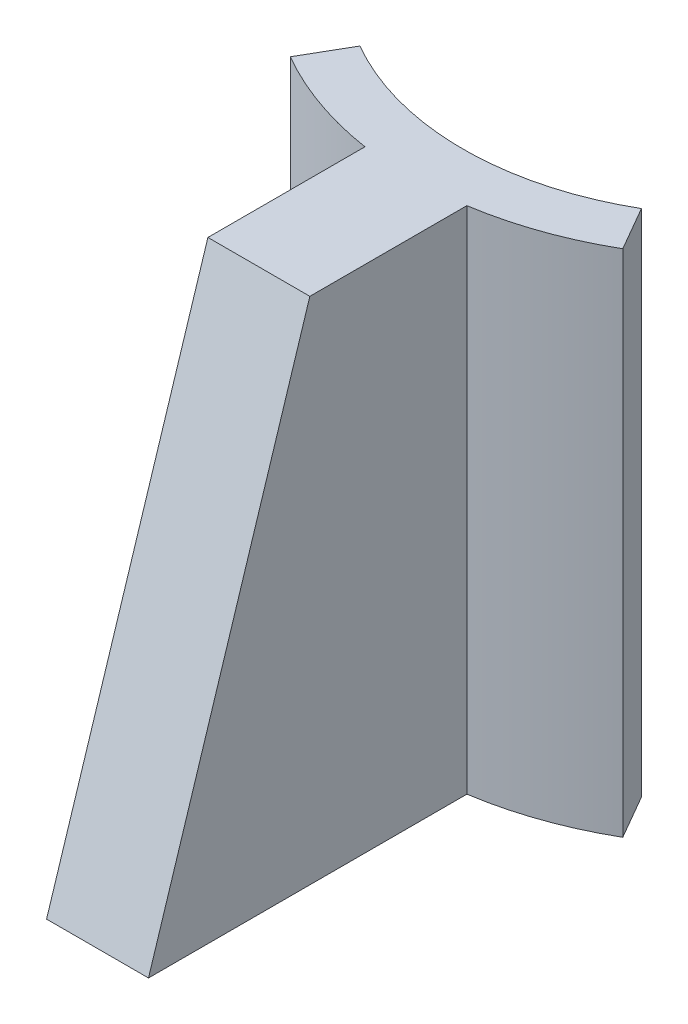
SolidWorks part; units mm, degrees
ref_plane "Front Plane" through (0, 0, 0) normal (0, 0, 1) x (1, 0, 0)
ref_plane "Top Plane" through (0, 0, 0) normal (0, 1, 0) x (1, 0, 0)
ref_plane "Right Plane" through (0, 0, 0) normal (1, 0, 0) x (0, 0, -1)
sketch "Sketch1" plane through (0, 0, 0) normal (1, 0, 0) x (0, 0, -1)
  line L0 (-3.2619, 9) -> (-4.7638, 9)
  line L1 (-3.2619, 4) -> (-6.3465, 4)
  line L2 (-6.3465, 4) -> (-4.7638, 9)
  line L9 (-3.2619, 9) -> (-2.8366, 9)
  line L11 (-3.2619, 4) -> (-2.8366, 4)
  line L12 (-2.8366, 9) -> (-2.8366, 4)
extrude "Boss-Extrude1" add sketch "Sketch1" along normal blind 0.5 and the other way blind 0.5 contours L12 L9 L0 L2 L1 L11 region at (0, 6.2574, 4.2343)
ref_plane "Plane1" through (0, 6.5, 0) normal (0, 1, 0) x (1, 0, 0)
sketch "Sketch2" plane through (0, 6.5, 0) normal (0, 1, 0) x (1, 0, 0)
  line L0 (0, -2.7619) -> (0, -3.2619)
  line L1 (-1.381, -2.3919) -> (-1.631, -2.8249)
  line L2 (1.381, -2.3919) -> (1.631, -2.8249)
  arc A0 (-1.631, -2.8249) -> (0, -3.2619) centre (0, 0) ccw
  arc A1 (-1.381, -2.3919) -> (0, -2.7619) centre (0, 0) ccw
  circle A2 centre (0, 0) radius 3.8 construction
  arc A3 (0, -3.2619) -> (1.631, -2.8249) centre (0, 0) ccw
  arc A4 (0, -2.7619) -> (1.381, -2.3919) centre (0, 0) ccw
  dimension "D3" = 0.5
  dimension "D4" = 0.5381
  dimension "D1" = 60
extrude "Boss-Extrude2" add sketch "Sketch2" along normal blind 2.5 and the other way blind 2.5 contours L2 A4 A1 L1 A0 A3
